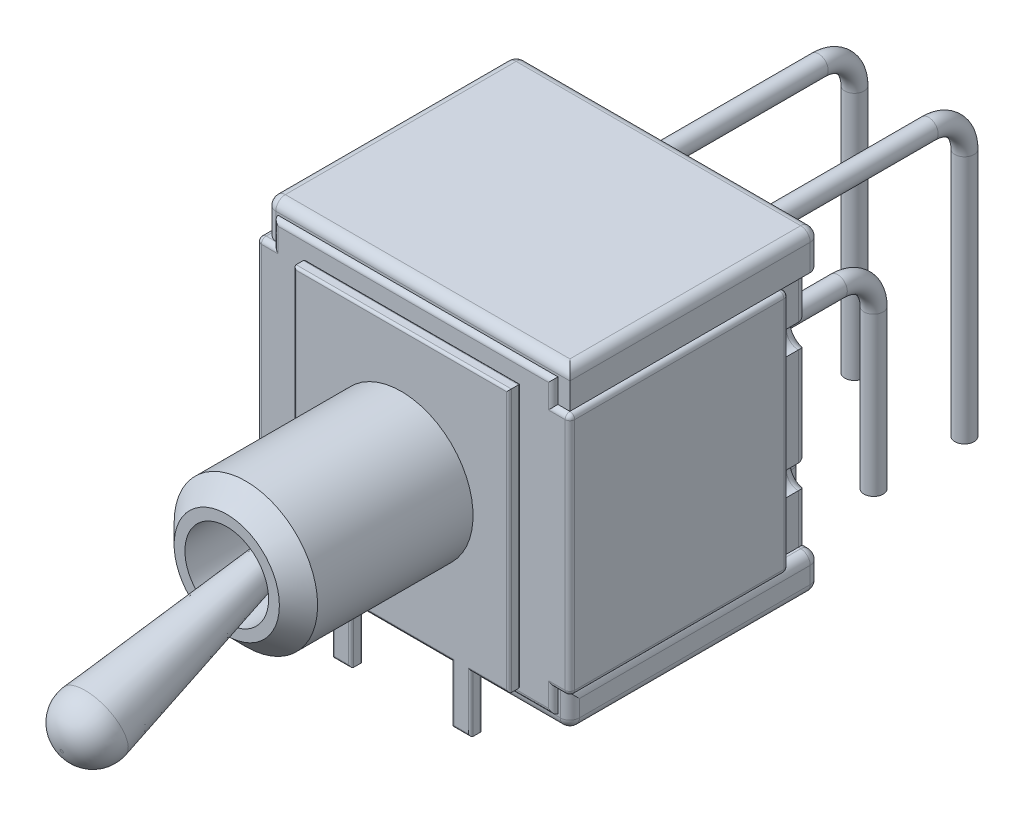
SolidWorks part; units mm, degrees
ref_plane "Спереди" through (0, 0, 0) normal (0, 0, 1) x (1, 0, 0)
ref_plane "Сверху" through (0, 0, 0) normal (0, 1, 0) x (1, 0, 0)
ref_plane "Справа" through (0, 0, 0) normal (1, 0, 0) x (0, 0, -1)
sketch "Эскиз1" plane through (0, 0, 0) normal (0, 1, 0) x (1, 0, 0)
  line L0 (-2.3, 0) -> (-2.3, -3.8) construction
  line L1 (-2.3, 0) -> (-2.3, 3.8) construction
  line L2 (2.3, 0) -> (2.3, 3.8) construction
  line L3 (2.3, 0) -> (2.3, -3.8) construction
  line L4 (-2.5, -16.4984) -> (2.5, -16.4984) construction
  line L5 (-2.3, 0) -> (2.3, 0) construction
  circle A0 centre (-2.3, 0) radius 0.95 construction
  circle A1 centre (2.3, 0) radius 0.95 construction
  circle A2 centre (-2.3, 3.8) radius 0.95 construction
  circle A3 centre (2.3, 3.8) radius 0.95 construction
  circle A4 centre (-2.3, -3.8) radius 0.95 construction
  circle A5 centre (2.3, -3.8) radius 0.95 construction
  circle A6 centre (-2.5, -16.4984) radius 0.95 construction
  circle A7 centre (2.5, -16.4984) radius 0.95 construction
  point P17 (0, -16.4984)
  point P18 (0, 0)
  point P19 (0, 0)
  point P20 (0, 0)
  dimension "D2" = 1.9
  dimension "D1" = 3.8
  dimension "D3" = 12.7
  dimension "D4" = 5
  dimension "D5" = 4.6
sketch "Эскиз2" plane through (0, 0, 0) normal (0, 1, 0) x (1, 0, 0)
  circle A5 centre (2.3, -3.8) radius 0.4
ref_plane "Плоскость1" through (2.3, 0, 0) normal (1, 0, 0) x (0, 0, -1)
sketch "Эскиз10" plane through (2.3, 0, 0) normal (1, 0, 0) x (0, 0, -1)
  line L0 (-3.8, 0) -> (-3.8, 1.3)
  line L1 (-5.3, 2.8) -> (-6.3, 2.8)
  arc A0 (-3.8, 1.3) -> (-5.3, 2.8) centre (-5.3, 1.3) ccw
  point P6 (-3.8, 2.8)
  dimension "D3" = 1.5
  dimension "D1" = 2.8
  dimension "D2" = 2.5
sweep "По траектории8" add profiles "Эскиз2" path "Эскиз10"
sketch "Эскиз11" plane through (0, 0, 0) normal (0, 1, 0) x (1, 0, 0)
  circle A0 centre (2.3, 0) radius 0.4
sketch "Эскиз12" plane through (2.3, 0, 0) normal (1, 0, 0) x (0, 0, -1)
  line L0 (0, 0) -> (0, 5.1)
  line L1 (-1.5, 6.6) -> (-6.3, 6.6)
  arc A0 (0, 5.1) -> (-1.5, 6.6) centre (-1.5, 5.1) ccw
  point P3 (0, 0)
  point P5 (0, 0)
  point P8 (0, 6.6)
  dimension "D3" = 1.5
  dimension "D1" = 6.3
  dimension "D2" = 6.6
sweep "По траектории9" add profiles "Эскиз11" path "Эскиз12"
sketch "Эскиз14" plane through (0, 0, 0) normal (0, 1, 0) x (1, 0, 0)
  circle A0 centre (2.3, 3.8) radius 0.4
sketch "Эскиз15" plane through (2.3, 0, 0) normal (1, 0, 0) x (0, 0, -1)
  line L0 (3.8, 0) -> (3.8, 8.9)
  line L1 (2.3, 10.4) -> (-6.3, 10.4)
  arc A0 (3.8, 8.9) -> (2.3, 10.4) centre (2.3, 8.9) ccw
  point P6 (3.8, 10.4)
  dimension "D3" = 1.5
  dimension "D1" = 10.4
  dimension "D2" = 10.1
sweep "По траектории10" add profiles "Эскиз14" path "Эскиз15"
pattern_linear "Линейный массив1" count 2 spacing 4.6 along (-1, 0, 0) of bodies 107 108 109
sketch "Эскиз16" plane through (0, 0, 0) normal (0, 1, 0) x (1, 0, 0)
  circle A0 centre (2.3, -3.8) radius 0.4
  circle A1 centre (2.3, 0) radius 0.4
  circle A2 centre (2.3, 3.8) radius 0.4
  circle A3 centre (-2.3, -3.8) radius 0.4
  circle A4 centre (-2.3, 0) radius 0.4
  circle A5 centre (-2.3, 3.8) radius 0.4
extrude "Бобышка-Вытянуть1" add sketch "Эскиз16" against normal blind 1.5
sketch "Эскиз17" plane through (0, 0, 6.3) normal (0, 0, 1) x (1, 0, 0)
  line L0 (-2.3, 6.6) -> (2.3, 6.6) construction
  line L2 (-6.35, 13.2) -> (6.35, 13.2)
  line L3 (-6.35, 13.2) -> (-6.35, 0)
  line L4 (-6.35, 0) -> (6.35, 0)
  line L5 (6.35, 13.2) -> (6.35, 0)
  line L6 (-6.35, 13.2) -> (6.35, 0) construction
  line L7 (-6.35, 0) -> (6.35, 13.2) construction
  point P0 (0, 6.6)
  dimension "D1" = 13.2
  dimension "D2" = 12.7
extrude "Бобышка-Вытянуть2" add sketch "Эскиз17" along normal blind 10.45 separate body
sketch "Эскиз18" plane through (0, 0, 16.75) normal (0, 0, 1) x (1, 0, 0)
  line L0 (6.35, 13.2) -> (-6.35, 13.2) construction
  line L1 (5.85, 0.5) -> (-5.85, 0.5)
  line L2 (5.85, 0.5) -> (5.85, 12.7)
  line L3 (5.85, 12.7) -> (-5.85, 12.7)
  line L4 (-5.85, 0.5) -> (-5.85, 12.7)
  line L5 (5.85, 0.5) -> (-5.85, 12.7) construction
  line L6 (5.85, 12.7) -> (-5.85, 0.5) construction
  line L7 (-6.35, 0) -> (6.35, 0) construction
  line L8 (-6.35, 13.2) -> (-6.35, 0) construction
  line L9 (6.35, 0) -> (6.35, 13.2) construction
  point P0 (0, 6.6)
  dimension "D1" = 0.5
  dimension "D2" = 0.5
  dimension "D3" = 0.5
  dimension "D4" = 0.5
extrude "Вырез-Вытянуть1" cut sketch "Эскиз18" against normal blind 0.5
sketch "Эскиз19" plane through (0, 0, 16.25) normal (0, 0, 1) x (1, 0, 0)
  line L1 (5.85, 0.5) -> (-5.85, 0.5)
  line L2 (5.85, 0.5) -> (5.85, 12.7)
  line L3 (5.85, 12.7) -> (-5.85, 12.7)
  line L4 (-5.85, 0.5) -> (-5.85, 12.7)
  line L5 (5.85, 0.5) -> (-5.85, 12.7) construction
  line L6 (5.85, 12.7) -> (-5.85, 0.5) construction
  point P0 (0, 6.6)
extrude "Бобышка-Вытянуть3" add sketch "Эскиз19" along normal blind 0.7 separate body
sketch "Эскиз20" plane through (0, 0, 16.75) normal (0, 0, 1) x (1, 0, 0)
  line L11 (-5.85, 12.7) -> (-5.85, 0.5) construction
  line L12 (-5.85, 11.7) -> (-6.35, 11.7)
  line L13 (-5.85, 11.7) -> (-5.85, 1.5)
  line L14 (-5.85, 1.5) -> (-6.35, 1.5)
  line L15 (-6.35, 11.7) -> (-6.35, 1.5)
  line L16 (5.85, 0.5) -> (5.85, 12.7) construction
  line L17 (5.85, 11.7) -> (6.35, 11.7)
  line L18 (5.85, 11.7) -> (5.85, 1.5)
  line L19 (5.85, 1.5) -> (6.35, 1.5)
  line L20 (6.35, 11.7) -> (6.35, 1.5)
  line L21 (6.35, 0) -> (6.35, 13.2) construction
  line L22 (-6.35, 13.2) -> (-6.35, 0) construction
  line L23 (-5.85, 0.5) -> (5.85, 0.5) construction
  line L24 (5.85, 12.7) -> (-5.85, 12.7) construction
  line L25 (5.85, 12.7) -> (-5.85, 12.7) construction
  point P18 (-6.1, 1.5)
  dimension "D1" = 1
  dimension "D2" = 1
  dimension "D3" = 1
  dimension "D4" = 1
extrude "Вырез-Вытянуть2" cut sketch "Эскиз20" against normal up to surface (10.45 mm away) up to face at (0, 6.6, 6.3)
sketch "Эскиз21" plane through (0, 0, 6.3) normal (0, 0, -1) x (-1, 0, 0)
  line L0 (-5.85, 6.6) -> (5.85, 6.6) construction
  line L1 (-5.85, 1.5) -> (-5.85, 11.7) construction
  line L2 (5.85, 11.7) -> (5.85, 1.5) construction
  line L3 (-5.85, 6.6) -> (-5.85, 11.7) construction
  circle A0 centre (-5.85, 9.15) radius 0.5
  circle A1 centre (5.85, 9.15) radius 0.5
  circle A2 centre (5.85, 4.05) radius 0.5
  circle A3 centre (-5.85, 4.05) radius 0.5
  point P12 (0, 0)
  point P13 (0, 0)
  dimension "D1" = 1
extrude "Вырез-Вытянуть3" cut sketch "Эскиз21" against normal blind 2
sketch "Эскиз22" plane through (0, 0, 16.95) normal (0, 0, 1) x (1, 0, 0)
  line L0 (-6.35, 1.5) -> (-6.35, 0) construction
  line L1 (5.85, 11.7) -> (6.55, 11.7)
  line L2 (5.85, 11.7) -> (5.85, 1.5)
  line L3 (5.85, 1.5) -> (6.55, 1.5)
  line L4 (6.55, 11.7) -> (6.55, 1.5)
  line L5 (-5.85, 11.7) -> (-6.55, 11.7)
  line L6 (-5.85, 11.7) -> (-5.85, 1.5)
  line L7 (-5.85, 1.5) -> (-6.55, 1.5)
  line L8 (-6.55, 11.7) -> (-6.55, 1.5)
  line L9 (6.35, 0) -> (6.35, 1.5) construction
  dimension "D1" = 0.2
  dimension "D2" = 0.2
extrude "Бобышка-Вытянуть4" add sketch "Эскиз22" against normal up to surface (8.65 mm away) separate body up to face at (5.6, 9.15, 8.3)
sketch "Эскиз23" plane through (0, 0, 8.3) normal (0, 0, -1) x (-1, 0, 0)
  line L0 (-5.85, 9.65) -> (-5.85, 8.65) construction
  line L1 (-5.85, 3.55) -> (-5.85, 4.55) construction
  line L2 (-5.85, 11.7) -> (-5.85, 1.5) construction
  line L3 (5.85, 8.65) -> (5.85, 9.65) construction
  line L4 (5.85, 1.5) -> (5.85, 11.7) construction
  line L5 (5.85, 4.55) -> (5.85, 3.55) construction
  line L6 (-5.85, 9.65) -> (-5.85, 11.7)
  line L7 (-5.85, 11.7) -> (-6.55, 11.7)
  line L8 (-6.55, 11.7) -> (-6.55, 1.5)
  line L9 (-6.55, 1.5) -> (-6.55, 11.7) construction
  line L10 (-6.55, 1.5) -> (-5.85, 1.5)
  line L11 (-5.85, 1.5) -> (-5.85, 3.55)
  line L12 (-5.85, 8.65) -> (-5.85, 4.55)
  line L13 (5.85, 8.65) -> (5.85, 4.55)
  line L14 (5.85, 3.55) -> (5.85, 1.5)
  line L15 (5.85, 1.5) -> (6.55, 1.5)
  line L16 (6.55, 1.5) -> (6.55, 11.7)
  line L17 (6.55, 11.7) -> (5.85, 11.7)
  line L18 (5.85, 11.7) -> (5.85, 9.65)
  arc A0 (-5.85, 9.65) -> (-5.85, 8.65) centre (-5.85, 9.15) cw
  arc A1 (-5.85, 8.65) -> (-5.85, 9.65) centre (-5.85, 9.15) ccw construction
  arc A2 (-5.85, 4.55) -> (-5.85, 3.55) centre (-5.85, 4.05) cw
  arc A3 (-5.85, 8.65) -> (-5.85, 9.65) centre (-5.85, 9.15) ccw construction
  arc A4 (5.85, 9.65) -> (5.85, 8.65) centre (5.85, 9.15) ccw
  arc A5 (5.85, 4.55) -> (5.85, 3.55) centre (5.85, 4.05) ccw
  arc A6 (5.85, 4.55) -> (5.85, 3.55) centre (5.85, 4.05) ccw construction
extrude "Бобышка-Вытянуть5" add sketch "Эскиз23" along normal blind 0.5 separate body
combine bodies "Соединить1" operation type add bodies to combine 127 125 121 124 126
fillet "Скругление1" radius 0.2 32 edges at (5.85, 6.6, 7.8) (5.35, 4.05, 7.8) (5.85, 2.525, 7.8) (6.2, 1.5, 7.8) (6.2, 11.7, 7.8) (5.85, 10.675, 7.8) (5.35, 9.15, 7.8) (-5.85, 10.675, 7.8) (-6.2, 11.7, 7.8) (-6.2, 1.5, 7.8) (-5.85, 2.525, 7.8) (-5.35, 4.05, 7.8) (-5.85, 6.6, 7.8) (-5.35, 9.15, 7.8) (6.55, 11.7, 12.375) (6.55, 6.6, 7.8) (6.55, 1.5, 12.375) (-6.55, 6.6, 7.8) (-6.55, 11.7, 12.375) (-6.55, 1.5, 12.375) (-6.55, 6.6, 16.95) (-6.2, 11.7, 16.95) (-5.85, 12.2, 16.95) (0, 12.7, 16.95) (5.85, 12.2, 16.95) (6.2, 11.7, 16.95) (6.55, 6.6, 16.95) (6.2, 1.5, 16.95) (5.85, 1, 16.95) (0, 0.5, 16.95) (-5.85, 1, 16.95) (-6.2, 1.5, 16.95)
sketch "Эскиз24" plane through (-6.55, 0, 0) normal (-1, 0, 0) x (0, 0, 1)
  line L0 (16.95, 11.5) -> (16.95, 1.7) construction
  line L1 (16.75, 11.5) -> (8, 11.5) construction
  line L2 (8, 1.7) -> (16.75, 1.7) construction
  line L3 (12.95, 1.7) -> (10.95, 1.7) construction
  line L4 (12.95, 11.5) -> (12.95, 1.7) construction
  line L5 (10.95, 11.5) -> (10.95, 1.7) construction
  text T0 "3A 250VAC" font "Arial" height 1.2
  text T1 "6A 125VAC" font "Arial" height 1.2
  dimension "D1" = 2
  dimension "D2" = 4
extrude "Вырез-Вытянуть4" cut sketch "Эскиз24" against normal blind 0.3
fillet "Скругление2" radius 0.4 32 edges at (5.35, 9.15, 6.3) (5.85, 10.675, 6.3) (6.1, 11.7, 6.3) (6.35, 12.45, 6.3) (-6.1, 11.7, 6.3) (-5.85, 10.675, 6.3) (-5.35, 9.15, 6.3) (-5.85, 6.6, 6.3) (-5.35, 4.05, 6.3) (-5.85, 2.525, 6.3) (-6.1, 1.5, 6.3) (6.1, 1.5, 6.3) (5.85, 2.525, 6.3) (5.35, 4.05, 6.3) (5.85, 6.6, 6.3) (-6.35, 0.75, 6.3) (-6.35, 1.5, 11.525) (-6.35, 0.75, 16.75) (6.35, 0.75, 16.75) (6.35, 1.5, 11.525) (6.35, 0.75, 6.3) (-6.35, 0, 11.525) (0, 0, 16.75) (6.35, 0, 11.525) (0, 0, 6.3) (-6.35, 12.45, 16.75) (-6.35, 11.7, 11.525) (-6.35, 12.45, 6.3) (6.35, 13.2, 11.525) (0, 13.2, 16.75) (-6.35, 13.2, 11.525) (0, 13.2, 6.3)
sketch "Эскиз25" plane through (0, 0, 16.95) normal (0, 0, 1) x (1, 0, 0)
  line L0 (-4.5, 11.8864) -> (4.5, 11.8864)
  line L1 (1.9, -1.5) -> (2.7, -1.5) construction
  line L3 (-2.1, 0.8919) -> (-2.1, -1.5)
  line L4 (-2.1, -1.5) -> (-2.9, -1.5)
  line L5 (-2.9, 0.8919) -> (-2.9, -1.5)
  line L7 (2.1, 0.8919) -> (2.1, -1.5)
  line L8 (2.1, -1.5) -> (2.9, -1.5)
  line L9 (2.9, 0.8919) -> (2.9, -1.5)
  line L10 (-2.7, -1.5) -> (-1.9, -1.5) construction
  line L11 (-2.1, 0.8919) -> (2.1, 0.8919)
  line L12 (-2.5, -1.5) -> (2.5, -1.5) construction
  line L13 (-4.5, 11.8864) -> (-4.5, 0.8919)
  line L14 (4.5, 11.8864) -> (4.5, 0.8919)
  line L15 (-2.9, 0.8919) -> (-4.5, 0.8919)
  line L16 (2.9, 0.8919) -> (4.5, 0.8919)
  point P2 (0, 11.8864)
  point P4 (0, -1.5)
  point P9 (4.3079, 1.2362)
  dimension "D1" = 5
extrude "Бобышка-Вытянуть6" add sketch "Эскиз25" along normal blind 0.5 separate body
fillet "Скругление3" radius 0.1 24 edges at (-3.7, 0.8919, 16.95) (-2.9, -0.3041, 16.95) (-2.5, -1.5, 16.95) (-2.1, -0.3041, 16.95) (0, 0.8919, 16.95) (2.1, -0.3041, 16.95) (2.5, -1.5, 16.95) (2.9, -0.3041, 16.95) (3.7, 0.8919, 16.95) (4.5, 6.3892, 16.95) (0, 11.8864, 16.95) (-4.5, 6.3892, 16.95) (0, 11.8864, 17.45) (4.5, 6.3892, 17.45) (3.7, 0.8919, 17.45) (2.9, -0.3041, 17.45) (2.5, -1.5, 17.45) (2.1, -0.3041, 17.45) (0, 0.8919, 17.45) (-2.1, -0.3041, 17.45) (-2.5, -1.5, 17.45) (-2.9, -0.3041, 17.45) (-3.7, 0.8919, 17.45) (-4.5, 6.3892, 17.45)
sketch "Эскиз26" plane through (0, 0, 17.45) normal (0, 0, 1) x (1, 0, 0)
  line L0 (-6.35, 6.6) -> (6.35, 6.6) construction
  line L1 (-6.35, 11.5) -> (-6.35, 1.7) construction
  line L2 (6.35, 1.7) -> (6.35, 11.5) construction
  circle A0 centre (0, 6.6) radius 3
  dimension "D1" = 6
extrude "Бобышка-Вытянуть7" add sketch "Эскиз26" along normal blind 7.3
chamfer "Фаска1" distance 0.8 angle 45 1 edges at (3, 6.6, 24.75)
sketch "Эскиз27" plane through (0, 0, 24.75) normal (0, 0, 1) x (1, 0, 0)
  circle A0 centre (0, 6.6) radius 1.75
  dimension "D1" = 3.5
extrude "Вырез-Вытянуть5" cut sketch "Эскиз27" against normal blind 3
sketch "Эскиз28" plane through (0, 0, 0) normal (1, 0, 0) x (0, 0, -1)
  line L0 (-24.75, 6.6) -> (-30.477, 6.6) construction
  line L1 (-32.076, 5.1057) -> (-31.224, 2.2293) construction
  line L2 (-24.75, 8.8) -> (-24.75, 4.4) construction
  line L3 (-21.75, 6.6) -> (-31.65, 3.6675) construction
  line L4 (-21.892, 7.0794) -> (-21.608, 6.1206) construction
  line L6 (-21.608, 6.1206) -> (-31.224, 2.2293)
  line L7 (-21.608, 6.1206) -> (-21.75, 6.6)
  line L8 (-21.75, 6.6) -> (-31.65, 3.6675)
  line L9 (-31.65, 3.6675) -> (-31.224, 2.2293)
  point P6 (-21.75, 6.6)
  point P11 (-31.65, 3.6675)
  dimension "D1" = 3
  dimension "D2" = 6.9
  dimension "D3" = 1
  dimension "D4" = 3
  dimension "D5" = 16.5
revolve "Повернуть1" add sketch "Эскиз28" angle 360 about L8 region at (0, 4.37, 27.3712)
fillet "Скругление4" radius 1.3 1 edges at (0, 5.1057, 32.076)
